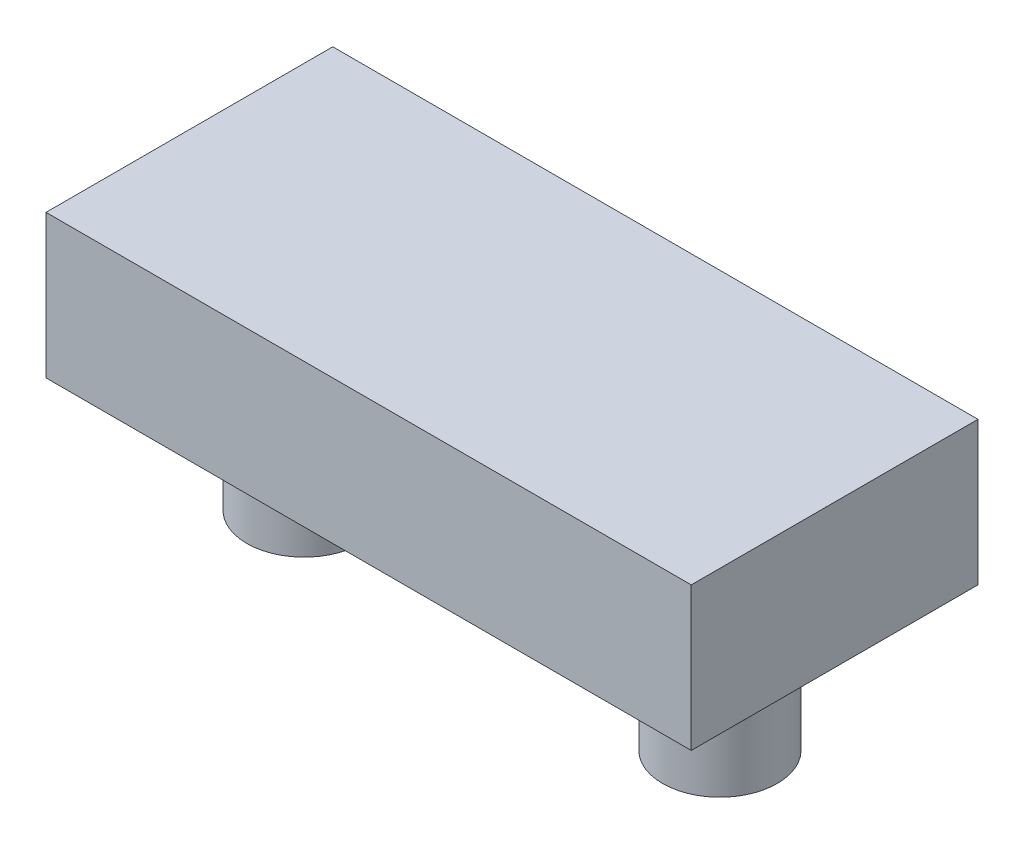
SolidWorks part; units mm, degrees
ref_plane "Front Plane" through (0, 0, 0) normal (0, 0, 1) x (1, 0, 0)
ref_plane "Top Plane" through (0, 0, 0) normal (0, 1, 0) x (1, 0, 0)
ref_plane "Right Plane" through (0, 0, 0) normal (1, 0, 0) x (0, 0, -1)
sketch "Sketch1" plane through (0, 0, 0) normal (0, 0, 1) x (1, 0, 0)
  line L0 (0, 0) -> (0, 640) construction
  line L2 (0, 640) -> (450, 640)
  line L3 (0, 640) -> (0, 540)
  line L4 (0, 540) -> (450, 540)
  line L5 (450, 640) -> (450, 540)
  dimension "D1" = 640
  dimension "D2" = 100
  dimension "D3" = 450
extrude "Boss-Extrude1" add sketch "Sketch1" along normal blind 200
sketch "Sketch2" plane through (0, 540, 0) normal (0, -1, 0) x (1, 0, 0)
  line L0 (0, 100) -> (450, 100) construction
  line L1 (0, 200) -> (0, 0) construction
  line L2 (450, 200) -> (450, 0) construction
  circle A0 centre (80, 100) radius 40
  circle A1 centre (370, 100) radius 40
  dimension "D1" = 80
  dimension "D3" = 80
  dimension "D2" = 80
  dimension "D4" = 80
extrude "Boss-Extrude2" add sketch "Sketch2" along normal blind 90
ref_plane "Plane1" through (0, 0, 100) normal (0, 0, -1) x (-1, 0, 0)
ref_axis "Axis1" through (80, 450, 100) along (0, 1, 0)
ref_axis "Axis2" through (370, 450, 100) along (0, 1, 0)
